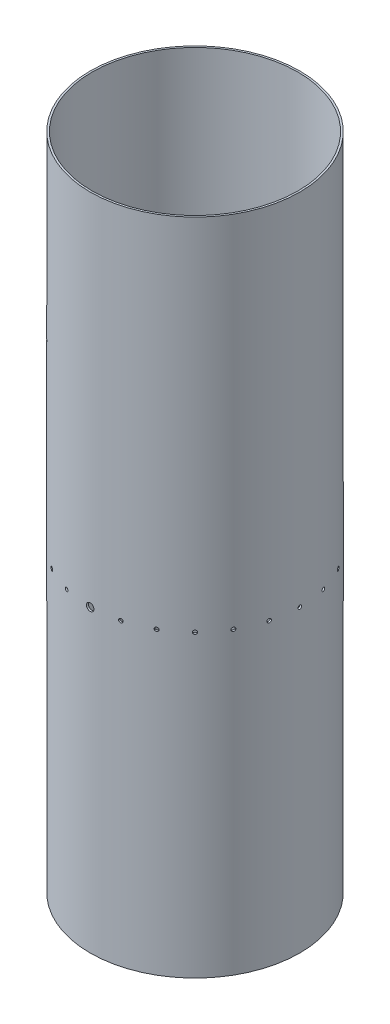
SolidWorks part; units mm, degrees
ref_plane "Front Plane" through (0, 0, 0) normal (0, 0, 1) x (1, 0, 0)
ref_plane "Top Plane" through (0, 0, 0) normal (0, 1, 0) x (1, 0, 0)
ref_plane "Right Plane" through (0, 0, 0) normal (1, 0, 0) x (0, 0, -1)
sketch "Sketch1" plane through (0, 0, 0) normal (0, 1, 0) x (1, 0, 0)
  circle A0 centre (0, 0) radius 88.9
  circle A1 centre (0, 0) radius 87.3125
  dimension "D1" = 177.8
  dimension "D2" = 174.625
extrude "Boss-Extrude1" add sketch "Sketch1" along normal blind 558.8
ref_plane "Plane1" through (0, 0, 88.9) normal (0, 0, 1) x (1, 0, 0)
sketch "Sketch10" plane through (0, 0, 88.9) normal (0, 0, 1) x (1, 0, 0)
  line L0 (88.9, 558.8) -> (-88.9, 558.8) construction
  circle A0 centre (0, 254) radius 1.5875
  dimension "D1" = 3.175
  dimension "D2" = 304.8
extrude "Cut-Extrude1" cut sketch "Sketch10" against normal blind 3.81
ref_axis "Axis1" through (0, 558.8, 0) along (0, -1, 0)
pattern_circular "CirPattern1" count 24 over 360 about axis through (0, 558.8, 0) along (0, -1, 0) of "Cut-Extrude1"
sketch "Sketch12" plane through (0, 0, 88.9) normal (0, 0, 1) x (1, 0, 0)
  circle A0 centre (0, 254) radius 3.175
  dimension "D1" = 6.35
extrude "Cut-Extrude2" cut sketch "Sketch12" against normal through all both and the other way through all
ref_axis "Axis2" through (0, 254, 87.0756) along (0, 0, 1)
sketch "Sketch15" plane through (0, 0, 0) normal (1, 0, 0) x (0, 0, -1)
  line L1 (0, 558.8) -> (0, 0) construction
  circle A2 centre (63.5, 431.8) radius 2.0955
  circle A3 centre (0, 254) radius 1.5875 construction
  dimension "D1" = 4.191
  dimension "D3" = 63.5
  dimension "D2" = 177.8
sketch "Sketch16" plane through (0, 0, 0) normal (0, 0, 1) x (1, 0, 0)
  line L0 (0, 558.8) -> (0, 0) construction
  line L1 (97.79, 0) -> (-97.79, 0) construction
  circle A0 centre (-63.5, 406.4) radius 2.0955
  dimension "D1" = 4.191
  dimension "D2" = 63.5
  dimension "D3" = 406.4
extrude "Cut-Extrude5" cut sketch "Sketch16" against normal through all both and the other way through all
